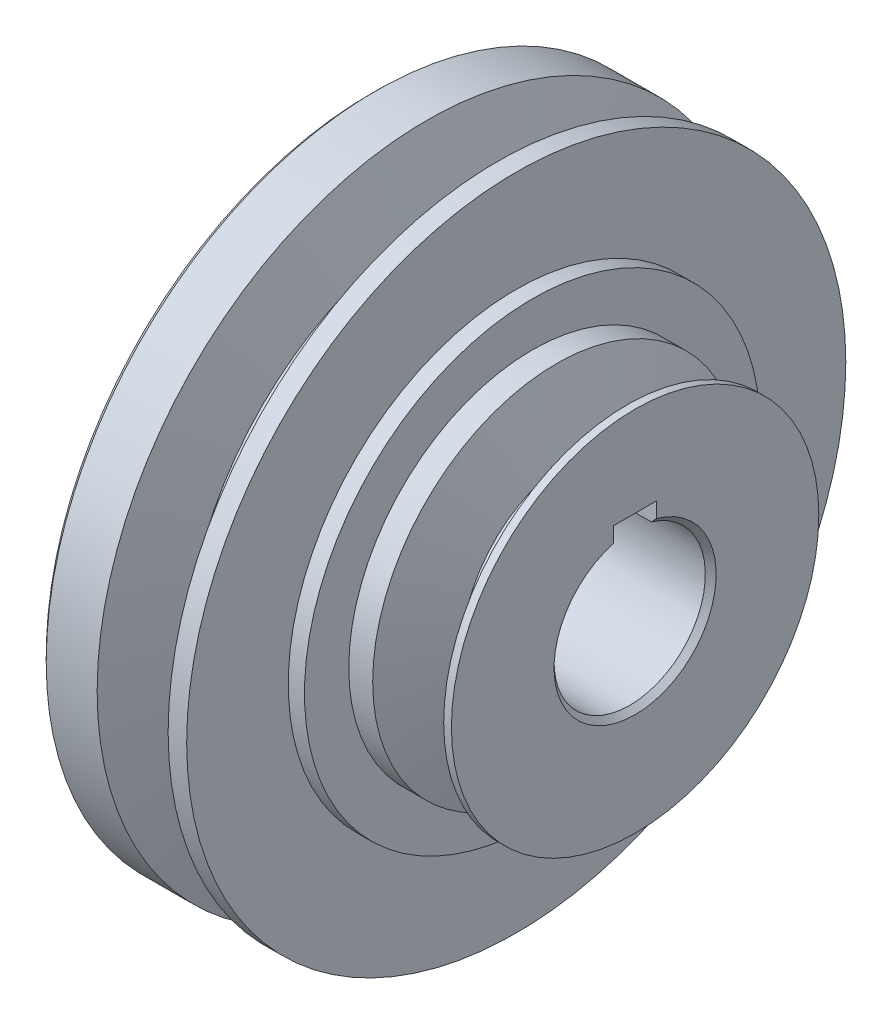
SolidWorks part; units mm, degrees
ref_plane "前视基准面" through (0, 0, 0) normal (0, 0, 1) x (1, 0, 0)
ref_plane "上视基准面" through (0, 0, 0) normal (0, 1, 0) x (1, 0, 0)
ref_plane "右视基准面" through (0, 0, 0) normal (1, 0, 0) x (0, 0, -1)
sketch "草图1" plane through (0, 0, 0) normal (1, 0, 0) x (0, 0, -1)
  circle A0 centre (0, 0) radius 61
  dimension "D1" = 122
extrude "凸台-拉伸1" add sketch "草图1" against normal blind 17 and the other way blind 10
sketch "草图2" plane through (0, 0, 0) normal (0, 1, 0) x (1, 0, 0)
  line L0 (0, 0) -> (0, 185.0201) construction
  line L1 (-20.1037, 57.5) -> (22.8414, 57.5) construction
  line L2 (10, 61) -> (-17, 61) construction
  line L3 (-5.5, 57.5) -> (5.5, 57.5) construction
  line L4 (-6.5701, 61) -> (-2.7484, 48.5)
  line L5 (-2.7484, 48.5) -> (2.7484, 48.5)
  line L6 (6.5701, 61) -> (2.7484, 48.5)
  line L7 (-6.5701, 61) -> (6.5701, 61)
  line L8 (0, 0) -> (69.5849, 0) construction
  point P9 (0, 57.5)
  point P14 (0, 48.5)
  dimension "D1" = 3.5
  dimension "D2" = 11
  dimension "D3" = 34
  dimension "D4" = 12.5
revolve "切除-旋转1" cut sketch "草图2" angle 360 about L8
sketch "草图3" plane through (-17, 0, 0) normal (-1, 0, 0) x (0, 0, 1)
  circle A0 centre (0, 0) radius 25
  dimension "D1" = 50
extrude "凸台-拉伸2" add sketch "草图3" along normal blind 19
sketch "草图4" plane through (-36, 0, 0) normal (-1, 0, 0) x (0, 0, 1)
  circle A0 centre (0, 0) radius 21
  dimension "D1" = 42
extrude "凸台-拉伸3" add sketch "草图4" along normal blind 6
sketch "草图5" plane through (-42, 0, 0) normal (-1, 0, 0) x (0, 0, 1)
  circle A0 centre (0, 0) radius 16.2
  dimension "D1" = 32.4
extrude "切除-拉伸1" cut sketch "草图5" against normal blind 11
sketch "草图6" plane through (-31, 0, 0) normal (-1, 0, 0) x (0, 0, 1)
  circle A0 centre (0, 0) radius 14
  dimension "D1" = 28
extrude "切除-拉伸2" cut sketch "草图6" against normal through all
sketch "草图8" plane through (-17, 0, 0) normal (-1, 0, 0) x (0, 0, 1)
  circle A0 centre (0, 0) radius 36.5 construction
  point P3 (0, 36.5)
  point P4 (0, -36.5)
  dimension "D1" = 73
hole_wizard "M10 螺纹孔1" positions "草图8" profile "草图9" tap size "M10" standard "GB"
sketch "草图9" plane through (-17, -36.5, 0) normal (0, 1, 0) x (0, 0, 1)
  line L0 (0, 0) -> (0, 20)
  line L1 (0, 20) -> (4.25, 17.4463)
  line L2 (4.25, 17.4463) -> (4.25, 0)
  line L5 (4.25, 0) -> (0, 0)
  line L10 (0, 20) -> (-4.25, 17.4463) construction
  line L11 (0, -6.35) -> (0, 107.95) construction
  dimension "螺纹孔钻头直径" = 8.5
  dimension "螺纹孔钻头深度" = 20
  dimension "导头角度" = 118
cosmetic thread "孔螺纹线1" parameters "D1"=15, "D2"=10
cosmetic thread "孔螺纹线2" parameters "D1"=15, "D2"=10
sketch "草图10" plane through (10, 0, 0) normal (1, 0, 0) x (0, 0, -1)
  circle A0 centre (0, 0) radius 42.1959
extrude "undef" add sketch "草图10" along normal blind 3
sketch "草图11" plane through (13, 0, 0) normal (1, 0, 0) x (0, 0, -1)
  circle A0 centre (0, 0) radius 34
  dimension "D1" = 68
extrude "凸台-拉伸5" add sketch "草图11" along normal blind 19
sketch "草图12" plane through (0, 0, 0) normal (0, 0, 1) x (1, 0, 0)
  line L0 (24, 51.7316) -> (24, -42.5547) construction
  line L1 (32, -34) -> (32, 34) construction
  line L2 (18.5, 30.5) -> (29.5, 30.5) construction
  line L3 (32, 34) -> (13, 34) construction
  line L4 (21.2516, 21.5) -> (26.7484, 21.5)
  line L5 (21.2516, 21.5) -> (17.4299, 34)
  line L6 (26.7484, 21.5) -> (30.5701, 34)
  line L7 (17.4299, 34) -> (30.5701, 34)
  line L8 (0, 0) -> (65.7067, 0) construction
  point P13 (24, 21.5)
  dimension "D1" = 8
  dimension "D2" = 3.5
  dimension "D3" = 12.5
  dimension "D4" = 34
  dimension "D5" = 11
revolve "切除-旋转2" cut sketch "草图12" angle 360 about L8
sketch "草图7" plane through (-42, 0, 0) normal (-1, 0, 0) x (0, 0, 1)
  line L0 (0, 0) -> (0, 39.0529) construction
  line L1 (-4, 17.3) -> (4, 17.3)
  line L2 (4, 17.3) -> (4, 13.4164)
  line L3 (-4, 17.3) -> (-4, 13.4164)
  line L4 (0, -14) -> (24.6189, -14) construction
  circle A0 centre (0, 0) radius 14 construction
  arc A1 (-4, 13.4164) -> (4, 13.4164) centre (0, 0) ccw
  arc A2 (4, 13.4164) -> (0, 14) centre (0, 0) ccw construction
  arc A3 (0, 14) -> (-4, 13.4164) centre (0, 0) ccw construction
  point P10 (0, 17.3)
  dimension "D1" = 31.3
  dimension "D2" = 8
extrude "切除-拉伸3" cut sketch "草图7" against normal through all
chamfer "倒角1" distance 1 angle 45 2 edges at (32, -14, 0) (-17, 0, -61)
